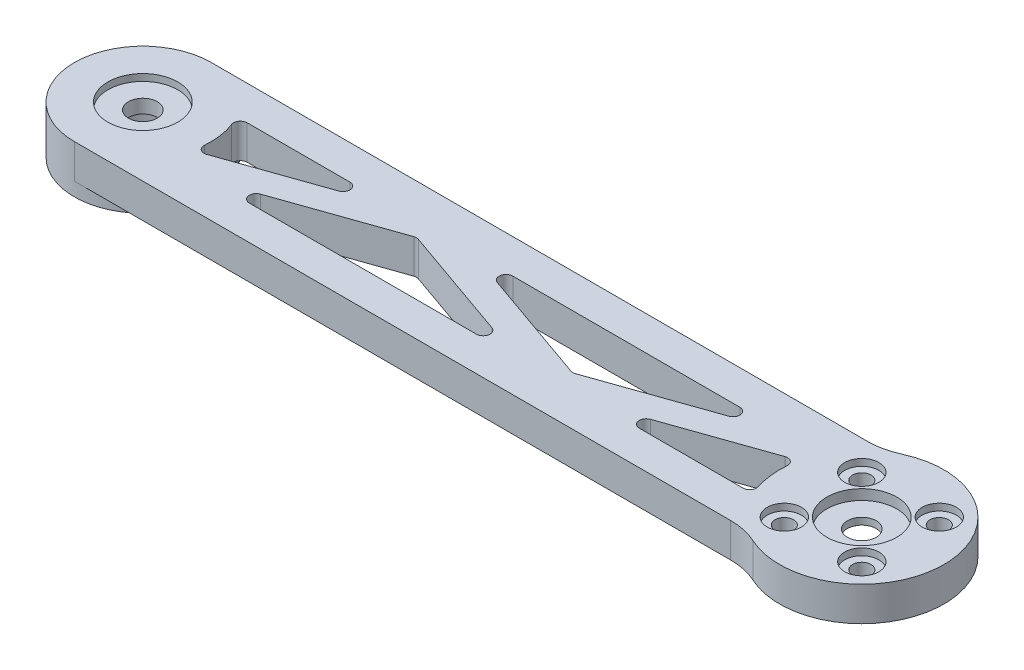
SolidWorks part; units mm, degrees
note: The reader was unsure of these and kept them because the rebuilt part matched: shared geometry of "草图1<4>", "草图1<9>", "草图1<10>", "草图1<11>", "草图1<15>", "草图1<16>".
material "三聚氰胺甲醛树脂"
ref_plane "前视基准面" through (0, 0, 0) normal (0, 0, 1) x (1, 0, 0)
ref_plane "上视基准面" through (0, 0, 0) normal (0, 1, 0) x (1, 0, 0)
ref_plane "右视基准面" through (0, 0, 0) normal (1, 0, 0) x (0, 0, -1)
sketch "草图1" plane through (0, 0, 0) normal (0, 1, 0) x (1, 0, 0)
  line L0 (-105, 10) -> (-6.6332, 10)
  line L1 (-105, -10) -> (-6.6332, -10)
  line L2 (-90.3034, -5) -> (-45.4221, -5)
  line L3 (-96.3397, 5) -> (-73.8991, 5)
  line L4 (-96.3397, -5) -> (-67.8627, 5) construction
  line L5 (-67.8627, 5) -> (-39.3857, -5) construction
  line L6 (-39.3857, -5) -> (-10.9087, 5) construction
  line L7 (-95.3236, -2.5234) -> (-73.8991, 5)
  line L8 (-90.3034, -5) -> (-67.8627, 2.8803)
  line L9 (-67.8627, 2.8803) -> (-45.4221, -5)
  line L10 (-61.8264, 5) -> (-39.3857, -2.8803)
  line L11 (-39.3857, -2.8803) -> (-16.9451, 5)
  line L12 (-33.3494, -5) -> (-11.7156, 2.5969)
  line L13 (-61.8264, 5) -> (-16.9451, 5)
  line L14 (-33.3494, -5) -> (-10.9087, -5)
  line L15 (0, 0) -> (-8.4853, 8.4853) construction
  line L16 (0, 0) -> (5.6569, -5.6569) construction
  line L17 (5.6569, 5.6569) -> (0, 0) construction
  line L18 (0, 0) -> (-5.6569, -5.6569) construction
  circle A0 centre (0, 0) radius 8 construction
  circle A1 centre (-5.6569, 5.6569) radius 1.35
  circle A2 centre (5.6569, 5.6569) radius 1.35
  circle A3 centre (5.6569, -5.6569) radius 1.35
  circle A4 centre (-5.6569, -5.6569) radius 1.35
  circle A5 centre (0, 0) radius 2.1
  circle A6 centre (0, 0) radius 5.1
  arc A7 (-11.7156, 2.5969) -> (-10.9087, -5) centre (0, 0) ccw
  arc A9 (-105, 10) -> (-105, -10) centre (-105, 0) ccw
  arc A10 (-6.6332, -10) -> (-6.6332, 10) centre (0, 0) ccw
  circle A11 centre (0, 0) radius 12 construction
  arc A12 (-95.3236, -2.5234) -> (-96.3397, 5) centre (-105, 0) ccw
  circle A13 centre (-105, 0) radius 10 construction
  circle A14 centre (-105, 0) radius 2.1
  circle A15 centre (-105, 0) radius 6.1
  circle A16 centre (0, 0) radius 6.1
  point P14 (0, 0)
  dimension "D1" = 16
  dimension "D2" = 2.7
  dimension "D3" = 10.2
  dimension "D4" = 4.2
  dimension "D5" = 24
  dimension "D6" = 12.2
  dimension "D7" = 20
  dimension "D17" = 4.2
  dimension "D18" = 12.2
  dimension "D19" = 2.7
  dimension "D20" = 2.7
  dimension "D21" = 2.7
  dimension "D8" = 105
  dimension "D9" = 5
  dimension "D10" = 5
  dimension "D11" = 2
  dimension "D12" = 2
  dimension "D13" = 2
  dimension "D14" = 2
  dimension "D15" = 2
  dimension "D16" = 2
extrude "凸台-拉伸1" add sketch "草图1" along normal blind 5
extrude "凸台-拉伸3" add sketch "草图1<4>" along normal blind 2 from offset 1.5 contours A16 A6 | A6 A5
sketch "草图1<4>" plane through (0, 0, 0) normal (0, 1, 0) x (1, 0, 0) same geometry as "草图1"
fillet "圆角1" radius 1 3 edges at (-73.8991, 2.5, -5) (-95.3236, 2.5, 2.5234) (-96.3397, 2.5, -5)
fillet "圆角2" radius 1 3 edges at (-45.4221, 2.5, 5) (-67.8627, 2.5, -2.8803) (-90.3034, 2.5, 5)
fillet "圆角3" radius 1 3 edges at (-16.9451, 2.5, -5) (-39.3857, 2.5, 2.8803) (-61.8264, 2.5, -5)
fillet "圆角4" radius 1 3 edges at (-33.3494, 2.5, 5) (-10.9087, 2.5, 5) (-11.7156, 2.5, -2.5969)
fillet "圆角5" radius 10 2 edges at (-6.6332, 2.5, 10) (-6.6332, 2.5, -10)
extrude "凸台-拉伸4" add sketch "草图1<9>" along normal blind 4
sketch "草图1<9>" plane through (0, 0, 0) normal (0, 1, 0) x (1, 0, 0) same geometry as "草图1"
extrude "凸台-拉伸5" add sketch "草图1<10>" along normal blind 2 from offset 2 contours A15 A14
sketch "草图1<10>" plane through (0, 0, 0) normal (0, 1, 0) x (1, 0, 0) same geometry as "草图1"
sketch "草图2" plane through (0, 0, 0) normal (0, -1, 0) x (1, 0, 0)
  arc A1 (-105, 10) -> (-105, -10) centre (-105, 0) ccw construction
  circle A3 centre (-105, 0) radius 10
  circle A4 centre (-105, 0) radius 6.1
  dimension "D1" = 12.2
extrude "凸台-拉伸7" add sketch "草图1<11>" along normal blind 3.5
sketch "草图1<11>" plane through (0, 0, 0) normal (0, 1, 0) x (1, 0, 0) same geometry as "草图1"
extrude "切除-拉伸-薄壁1" cut sketch "草图1<15>" against normal blind 1 from surface at 5 thin contours A3 | A4 | A1 | A2
sketch "草图1<15>" plane through (0, 0, 0) normal (0, 1, 0) x (1, 0, 0) same geometry as "草图1"
extrude "凸台-拉伸8" add sketch "草图2" along normal blind 2
extrude "切除-拉伸1" cut sketch "草图1<16>" along normal blind 1.5 contours A16 A6
sketch "草图1<16>" plane through (0, 0, 0) normal (0, 1, 0) x (1, 0, 0) same geometry as "草图1"
sketch "草图3" plane through (0, 5, 0) normal (0, 1, 0) x (1, 0, 0)
  circle A0 centre (-105, 0) radius 5.1
  circle A1 centre (-105, 0) radius 6.1
  dimension "D1" = 10.2
  dimension "D2" = 12.2
extrude "凸台-拉伸9" add sketch "草图3" against normal blind 1
sketch "草图4" plane through (0, 1.5, 0) normal (0, -1, 0) x (1, 0, 0)
  line L1 (3.9837, 0) -> (1.9919, 3.45)
  line L2 (1.9919, 3.45) -> (-1.9919, 3.45)
  line L3 (-1.9919, 3.45) -> (-3.9837, 0)
  line L4 (-3.9837, 0) -> (-1.9919, -3.45)
  line L5 (-1.9919, -3.45) -> (1.9919, -3.45)
  line L6 (1.9919, -3.45) -> (3.9837, 0)
  circle A0 centre (0, 0) radius 3.45 construction
  dimension "D1" = 6.9
extrude "切除-拉伸2" cut sketch "草图4" against normal blind 1
